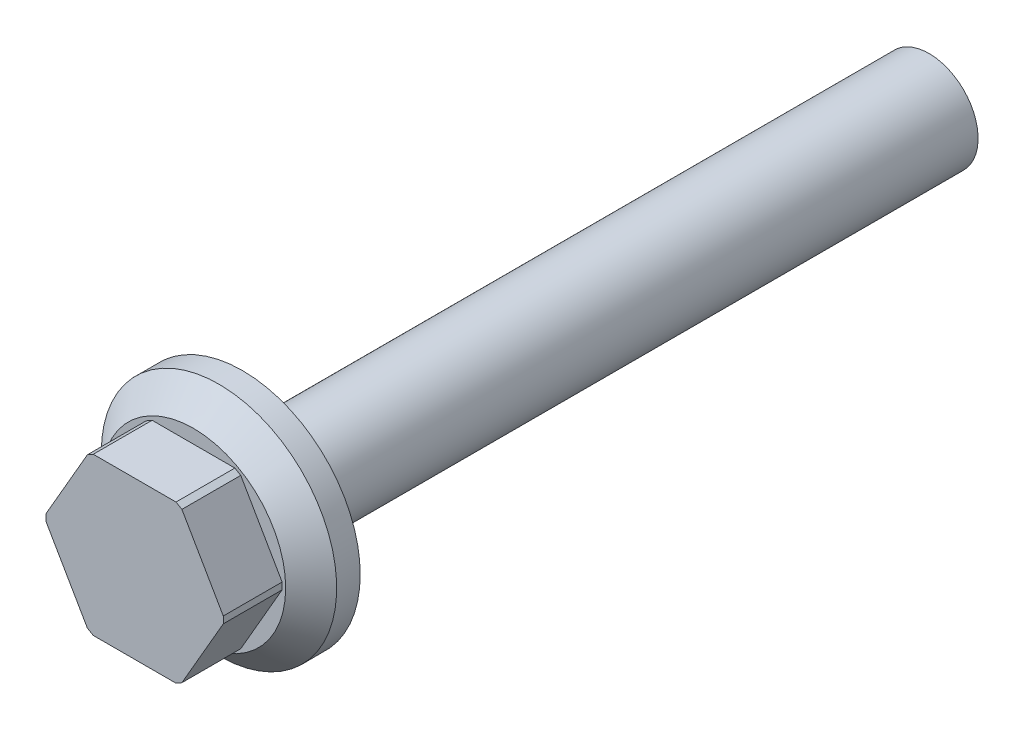
SolidWorks part; units mm, degrees
ref_plane "Płaszczyzna przednia" through (0, 0, 0) normal (0, 0, 1) x (1, 0, 0)
ref_plane "Płaszczyzna górna" through (0, 0, 0) normal (0, 1, 0) x (1, 0, 0)
ref_plane "Płaszczyzna prawa" through (0, 0, 0) normal (1, 0, 0) x (0, 0, -1)
sketch "Sketch1" plane through (0, 0, 0) normal (0, 1, 0) x (1, 0, 0)
  line L0 (0, 0) -> (2.5, 0)
  line L1 (2.5, 0) -> (2.5, 35)
  line L2 (2.5, 35) -> (0, 35)
  line L3 (0, 35) -> (0, 0)
  dimension "D1" = 35
  dimension "D2" = 2.5
revolve "Revolve1" add sketch "Sketch1" angle 360 about L3
sketch "Sketch2" plane through (0, 0, 0) normal (0, 0, 1) x (1, 0, 0)
  circle A0 centre (0, 0) radius 6
  dimension "D1" = 12
extrude "Boss-Extrude1" add sketch "Sketch2" along normal blind 1
sketch "Sketch3" plane through (0, 0, 1) normal (0, 0, 1) x (1, 0, 0)
  line L1 (-3.8945, 2.4832) -> (-4.0978, -2.1311) construction
  line L2 (-4.0978, -2.1311) -> (-0.2033, -4.6143) construction
  line L3 (-0.2033, -4.6143) -> (3.8945, -2.4832) construction
  line L4 (3.8945, -2.4832) -> (4.0978, 2.1311) construction
  line L5 (4.0978, 2.1311) -> (0.2033, 4.6143) construction
  line L6 (0.2033, 4.6143) -> (-3.8945, 2.4832) construction
  circle A0 centre (0, 0) radius 4 construction
  circle A1 centre (0, 0) radius 4.4
  dimension "D2" = 8.8
  dimension "D1" = 8
extrude "Boss-Extrude2" add sketch "Sketch3" along normal blind 1.5
chamfer "Chamfer1" distance 1.8 angle 45 1 edges at (4.4, 0, 1)
sketch "Sketch4" plane through (0, 0, 2.5) normal (0, 0, 1) x (1, 0, 0)
  line L1 (-2.3094, 4) -> (-4.6188, 0)
  line L2 (-4.6188, 0) -> (-2.3094, -4)
  line L3 (-2.3094, -4) -> (2.3094, -4)
  line L4 (2.3094, -4) -> (4.6188, 0)
  line L5 (4.6188, 0) -> (2.3094, 4)
  line L6 (2.3094, 4) -> (-2.3094, 4)
  circle A0 centre (0, 0) radius 4 construction
  dimension "D1" = 8
extrude "Boss-Extrude3" add sketch "Sketch4" along normal blind 3 and the other way blind 1.5
chamfer "Chamfer2" distance 0.2 angle 30 6 edges at (4.6188, 0, 4) (-4.6188, 0, 4) (-2.3094, -4, 4) (2.3094, -4, 4) (2.3094, 4, 4) (-2.3094, 4, 4) first distance on face at (3.4641, -2, 4) first distance on face at (-3.4641, -2, 4) first distance on face at (0, 4, 4)
